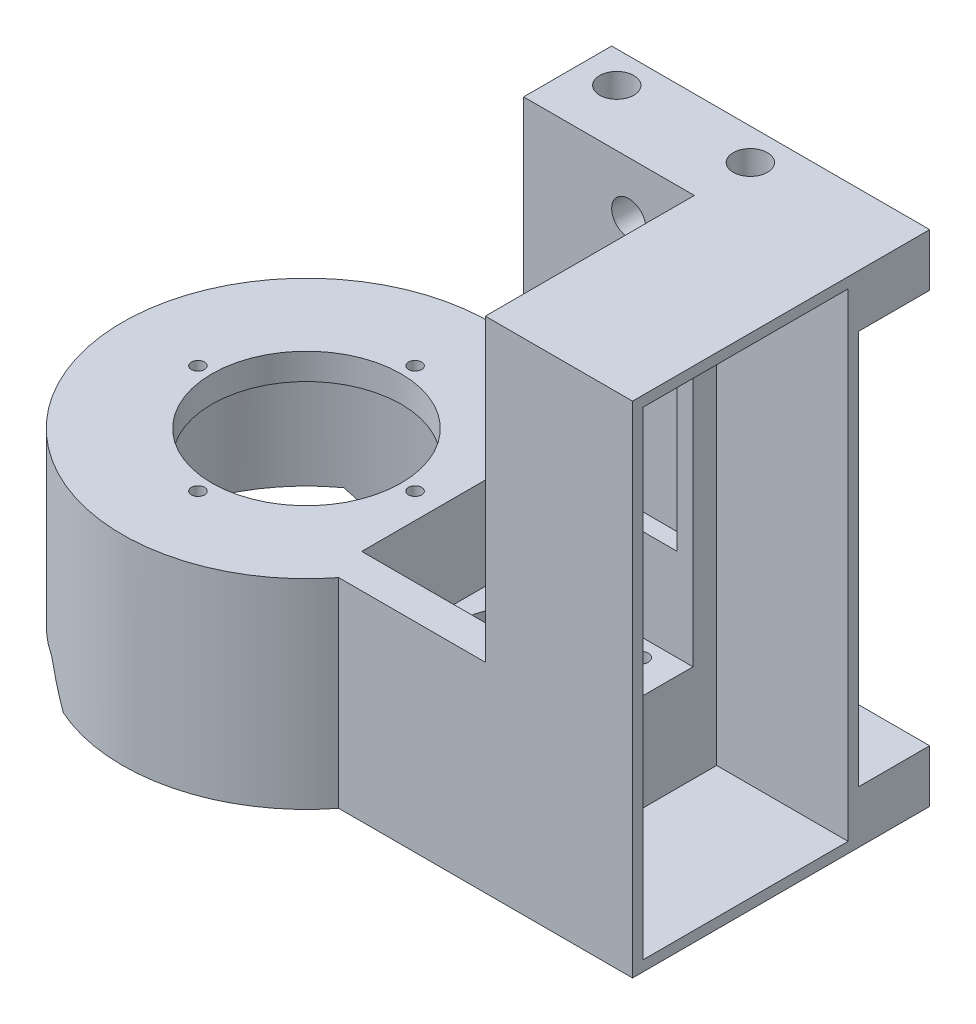
SolidWorks part; units mm, degrees
ref_plane "Front Plane" through (0, 0, 0) normal (0, 0, 1) x (1, 0, 0)
ref_plane "Top Plane" through (0, 0, 0) normal (0, 1, 0) x (1, 0, 0)
ref_plane "Right Plane" through (0, 0, 0) normal (1, 0, 0) x (0, 0, -1)
sketch "Sketch1" plane through (0, 0, 0) normal (0, 1, 0) x (1, 0, 0)
  circle A0 centre (0, 0) radius 20.64 construction
  circle A1 centre (0, 20.64) radius 1.25
  circle A2 centre (-20.64, 0) radius 1.25
  circle A3 centre (0, -20.64) radius 1.25
  circle A4 centre (20.64, 0) radius 1.25
  circle A5 centre (0, 0) radius 18
  circle A6 centre (0, 0) radius 26
  dimension "D1" = 41.28
  dimension "D2" = 2.5
  dimension "D3" = 52
extrude "Boss-Extrude1" add sketch "Sketch1" along normal blind 5
sketch "Sketch2" plane through (0, 5, 0) normal (0, 1, 0) x (1, 0, 0)
  circle A0 centre (0, 0) radius 26
  circle A1 centre (0, 0) radius 35
extrude "Boss-Extrude2" add sketch "Sketch2" against normal blind 3
sketch "Sketch3" plane through (0, 2, 0) normal (0, -1, 0) x (1, 0, 0)
  circle A0 centre (0, 0) radius 35
  circle A1 centre (0, 0) radius 32.5
  circle A2 centre (0, 0) radius 35 construction
  dimension "D1" = 2.5
extrude "Boss-Extrude3" add sketch "Sketch3" along normal blind 35
sketch "Sketch4" plane through (0, 5, 0) normal (0, 1, 0) x (1, 0, 0)
  line L1 (25.5, -15) -> (39.0882, -15)
  line L2 (25.5, -15) -> (25.5, 15)
  line L3 (25.5, 15) -> (39.0882, 15)
  line L4 (39.0882, -15) -> (39.0882, 15)
  line L5 (25.5, -15) -> (39.0882, 15) construction
  line L6 (25.5, 15) -> (39.0882, -15) construction
  point P0 (32.2941, 0)
  point P5 (0, 0)
  dimension "D1" = 25.5
  dimension "D2" = 30
extrude "Cut-Extrude1" cut sketch "Sketch4" against normal blind 20
sketch "Sketch5" plane through (0, -15, 0) normal (0, 1, 0) x (1, 0, 0)
  line L0 (25.5, -15) -> (31.6228, -15) construction
  line L1 (25.5, 15) -> (55.5, 15)
  line L2 (25.5, 15) -> (25.5, -15)
  line L3 (25.5, -15) -> (55.5, -15)
  line L4 (55.5, 15) -> (55.5, -15)
  line L5 (25.5, 15) -> (55.5, -15) construction
  line L7 (29, -11.5) -> (52, -11.5) construction
  line L8 (29, -11.5) -> (29, 11.5) construction
  line L9 (29, 11.5) -> (52, 11.5) construction
  line L10 (52, -11.5) -> (52, 11.5) construction
  line L11 (29, -11.5) -> (52, 11.5) construction
  line L12 (29, 11.5) -> (52, -11.5) construction
  circle A0 centre (40.5, 0) radius 11.8163
  circle A1 centre (29, 11.5) radius 1.5
  circle A2 centre (52, 11.5) radius 1.5
  circle A3 centre (52, -11.5) radius 1.5
  circle A4 centre (29, -11.5) radius 1.5
  dimension "D2" = 3
  dimension "D1" = 23
extrude "Boss-Extrude4" add sketch "Sketch5" along normal blind 2.5
sketch "Sketch6" plane through (0, -33, 0) normal (0, -1, 0) x (1, 0, 0)
  line L1 (25.5, 15) -> (55.5, 15)
  line L2 (25.5, 15) -> (25.5, -15)
  line L3 (25.5, -15) -> (55.5, -15)
  line L4 (55.5, 15) -> (55.5, -15)
extrude "Cut-Extrude2" cut sketch "Sketch6" against normal up to surface (18 mm away) up to face at (43.4054, -15, 0)
sketch "Sketch7" plane through (0, 2, 0) normal (0, -1, 0) x (1, 0, 0)
  line L0 (25.5, -15) -> (25.5, 15) construction
  line L1 (28.8314, 15) -> (25.5, 15)
  line L2 (28.8314, 15) -> (28.8314, 17)
  line L3 (28.8314, 17) -> (23.5, 17)
  line L4 (23.5, 15) -> (23.5, 17)
  line L7 (23.5, 15) -> (23.5, -15)
  line L9 (25.5, 15) -> (25.5, -15)
  line L10 (25.5, -15) -> (28.8314, -15)
  line L11 (23.5, -15) -> (23.5, -17)
  line L12 (23.5, -17) -> (28.8314, -17)
  line L13 (28.8314, -15) -> (28.8314, -17)
  dimension "D1" = 2
  dimension "D2" = 2
  dimension "D3" = 2
extrude "Boss-Extrude5" add sketch "Sketch7" along normal up to surface (17 mm away) up to face at (35.3635, -15, 0)
sketch "Sketch8" plane through (55.5, 0, 0) normal (1, 0, 0) x (0, 0, -1)
  line L0 (-32.5, -33) -> (32.5, -33) construction
  line L1 (-21.5, 62) -> (21.5, 62)
  line L2 (-21.5, 62) -> (-21.5, -33)
  line L3 (-21.5, -33) -> (21.5, -33)
  line L4 (21.5, 62) -> (21.5, -33)
  line L6 (15, -12.5) -> (0, -12.5)
  line L7 (15, -12.5) -> (15, 44.2656)
  line L8 (15, 44.2656) -> (0, 44.2656)
  line L9 (0, -12.5) -> (0, 44.2656)
  dimension "D1" = 43
  dimension "D2" = 21.5
  dimension "D3" = 95
extrude "Boss-Extrude6" add sketch "Sketch8" along normal blind 3
sketch "Sketch9" plane through (0, -33, 0) normal (0, -1, 0) x (1, 0, 0)
  line L0 (31.6228, 15) -> (28.8314, 15) construction
  line L1 (55.5, 21.5) -> (26.2848, 21.5)
  line L2 (55.5, 21.5) -> (55.5, 15)
  line L3 (55.5, 15) -> (30.2271, 15)
  line L4 (26.2848, 21.5) -> (30.2271, 15)
  point P7 (26.2848, 21.5)
extrude "Boss-Extrude7" add sketch "Sketch9" against normal up to surface (38 mm away) up to face at (11.9057, 5, 0)
mirror "Mirror1" about plane through (0, 0, 0) normal (0, 0, 1) of "Boss-Extrude7"
sketch "Sketch10" plane through (58.5, 0, 0) normal (1, 0, 0) x (0, 0, -1)
  line L0 (-21.5, 62) -> (-21.5, -33) construction
  line L1 (-21.5, 62) -> (21.5, 62)
  line L2 (-21.5, 62) -> (-21.5, -33)
  line L3 (-21.5, -33) -> (21.5, -33)
  line L4 (21.5, 62) -> (21.5, -33)
  line L5 (21.5, 62) -> (-21.5, 62) construction
  line L7 (-19.5, 60) -> (19.5, 60)
  line L8 (-19.5, 60) -> (-19.5, -31)
  line L9 (-19.5, -31) -> (19.5, -31)
  line L10 (19.5, 60) -> (19.5, -31)
  dimension "D1" = 2
  dimension "D2" = 2
  dimension "D3" = 2
  dimension "D4" = 2
extrude "Boss-Extrude8" add sketch "Sketch10" along normal blind 25
sketch "Sketch11" plane through (0, -33, 0) normal (0, -1, 0) x (1, 0, 0)
  line L0 (83.5, -21.5) -> (55.5, -21.5) construction
  line L1 (0, -35) -> (83.5, -35)
  line L3 (27.6179, -21.5) -> (83.5, -21.5)
  line L4 (83.5, -35) -> (83.5, -21.5)
  arc A0 (27.6179, 21.5) -> (27.6179, -21.5) centre (0, 0) ccw construction
  arc A1 (0, -35) -> (27.6179, -21.5) centre (0, 0) ccw
  circle A2 centre (30, -29) radius 3.25
  circle A3 centre (55.4, -29) radius 3.25
  point P15 (0, 0)
  dimension "D1" = 6.5
  dimension "D2" = 25.4
  dimension "D3" = 30
  dimension "D4" = 6
extrude "Boss-Extrude9" add sketch "Sketch11" against normal blind 10
sketch "Sketch12" plane through (0, 62, 0) normal (0, 1, 0) x (1, 0, 0)
  line L1 (83.5, 35) -> (23.0324, 35)
  line L2 (83.5, 35) -> (83.5, 21.5)
  line L3 (83.5, 21.5) -> (23.0324, 21.5)
  line L4 (23.0324, 35) -> (23.0324, 21.5)
  circle A0 centre (30, 29) radius 3.25
  circle A1 centre (55.4, 29) radius 3.25
extrude "Boss-Extrude10" add sketch "Sketch12" against normal blind 10
sketch "Sketch13" plane through (0, 5, 0) normal (0, 1, 0) x (1, 0, 0)
  line L1 (23.0324, 21.5) -> (55.5, 21.5)
  line L2 (23.0324, 21.5) -> (23.0324, 18.25)
  line L3 (23.0324, 18.25) -> (55.5, 18.25)
  line L4 (55.5, 21.5) -> (55.5, 18.25)
  dimension "D1" = 3.25
extrude "Boss-Extrude11" add sketch "Sketch13" along normal up to surface (57 mm away) up to face at (54.0108, 62, -11.6667)
sketch "Sketch14" plane through (0, 0, -21.5) normal (0, 0, -1) x (-1, 0, 0)
  line L0 (-83.5, 52) -> (-23.0324, 52) construction
  line L1 (-49.0324, 52) -> (-37.0324, 52)
  line L2 (-49.0324, 52) -> (-49.0324, -23)
  line L3 (-49.0324, -23) -> (-37.0324, -23)
  line L4 (-37.0324, 52) -> (-37.0324, -23)
  line L5 (0, -23) -> (-83.5, -23) construction
  line L6 (-23.0324, 52) -> (-23.0324, 5) construction
  dimension "D1" = 14
  dimension "D2" = 12
extrude "Boss-Extrude12" add sketch "Sketch14" along normal up to surface (13.5 mm away) up to face at (41.75, -28, -35)
sketch "Sketch15" plane through (0, 0, -35) normal (0, 0, -1) x (-1, 0, 0)
  line L0 (-23.0324, 52) -> (-23.0324, 5) construction
  line L1 (-83.5, 62) -> (-23.0324, 62) construction
  circle A0 centre (-43.0324, 52) radius 3.25
  circle A1 centre (-43.0324, 26.6) radius 3.25
  dimension "D1" = 6.5
  dimension "D2" = 25.4
  dimension "D3" = 20
  dimension "D4" = 10
extrude "Cut-Extrude3" cut sketch "Sketch15" against normal through all
sketch "Sketch16" plane through (0, 0, 0) normal (0, 0, 1) x (1, 0, 0)
  line L1 (-37.8581, -35.3437) -> (-12.2659, -35.3437)
  line L2 (-37.8581, -35.3437) -> (-37.8581, -27.4598)
  line L3 (-37.8581, -27.4598) -> (-19.1713, -27.4598)
  line L4 (-12.2659, -35.3437) -> (-19.1713, -27.4598)
  point P4 (-12.2659, -35.3437)
extrude "Cut-Extrude4" cut sketch "Sketch16" against normal through all and the other way through all
